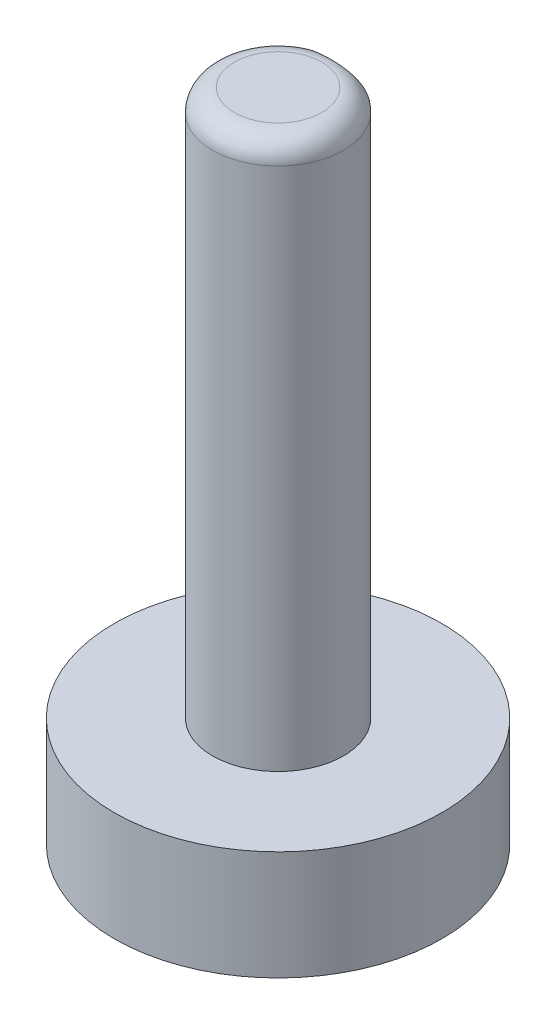
SolidWorks part; units mm, degrees
material "AISI 1020 Steel, Cold Rolled"
ref_plane "Front" through (0, 0, 0) normal (0, 0, 1) x (1, 0, 0)
ref_plane "Top" through (0, 0, 0) normal (0, 1, 0) x (1, 0, 0)
ref_plane "Right" through (0, 0, 0) normal (1, 0, 0) x (0, 0, -1)
sketch "Sketch1" plane through (0, 0, 0) normal (0, 1, 0) x (1, 0, 0)
  circle A0 centre (0, 0) radius 7.5
  dimension "D1" = 15
extrude "Boss-Extrude1" add sketch "Sketch1" along normal blind 5
sketch "Sketch2" plane through (0, 5, 0) normal (0, 1, 0) x (1, 0, 0)
  circle A0 centre (0, 0) radius 3
  dimension "D1" = 6
extrude "Boss-Extrude2" add sketch "Sketch2" along normal offset from surface (25 mm away) 30 up to face at (0, 0, 7.5)
sketch "Sketch3" plane through (0, 30, 0) normal (0, 1, 0) x (1, 0, 0)
  line L0 (0, 0) -> (0, -3) construction
  line L1 (-2.1316, 3.5908) -> (1.8, 3.5908)
  line L2 (-2.1316, 3.5908) -> (-2.1316, 2.4)
  line L3 (-2.1316, 2.4) -> (1.8, 2.4)
  line L4 (1.8, 3.5908) -> (1.8, 2.4)
  line L5 (-2.1316, 3.5908) -> (1.8, 2.4) construction
  line L6 (-2.1316, 2.4) -> (1.8, 3.5908) construction
  circle A0 centre (0, 0) radius 3 construction
  circle A1 centre (0, 0) radius 3 construction
  point P0 (-0.1658, 2.9954)
  dimension "D1" = 5.4
extrude "Cut-Extrude1" cut sketch "Sketch3" against normal blind 14
fillet "Fillet1" radius 1 1 edges at (0, 16, -2.4)
fillet "Fillet2" radius 1 1 edges at (0, 30, 3)
